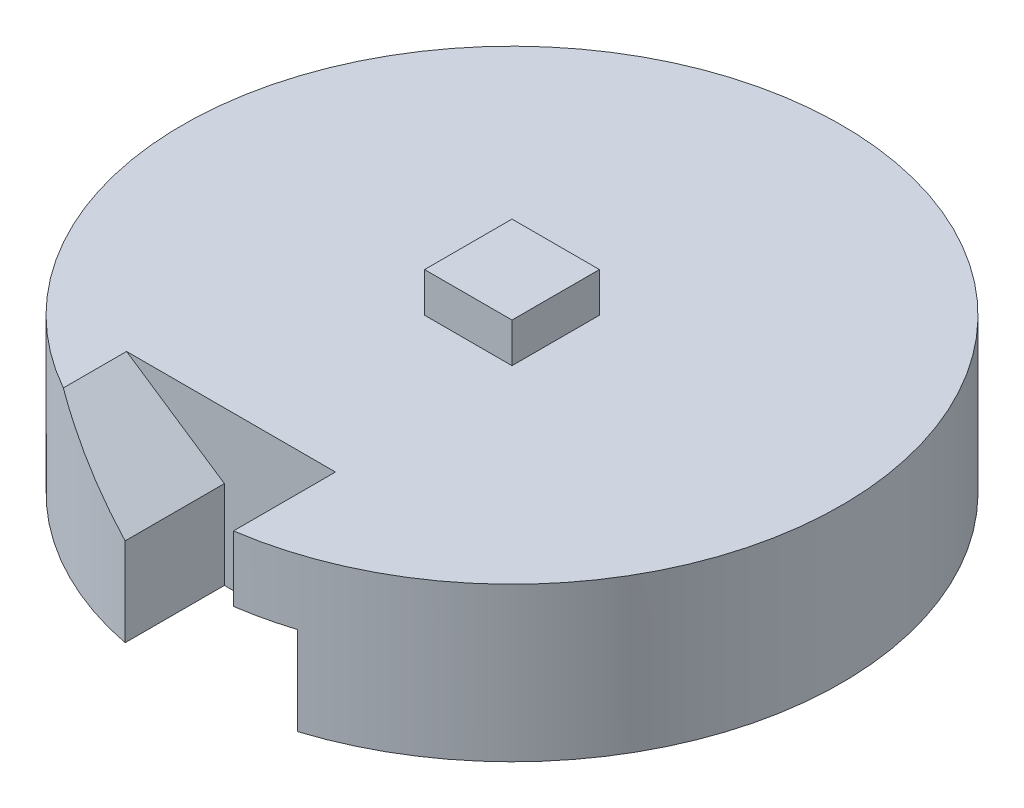
SolidWorks part; units mm, degrees
ref_plane "Front Plane" through (0, 0, 0) normal (0, 0, 1) x (1, 0, 0)
ref_plane "Top Plane" through (0, 0, 0) normal (0, 1, 0) x (1, 0, 0)
ref_plane "Right Plane" through (0, 0, 0) normal (1, 0, 0) x (0, 0, -1)
sketch "Sketch1" plane through (0, 0, 0) normal (0, 1, 0) x (1, 0, 0)
  circle A0 centre (0, 0) radius 37.5
extrude "Boss-Extrude1" add sketch "Sketch1" along normal blind 17.5 contours A0
sketch "Sketch2" plane through (0, 0, 0) normal (0, -1, 0) x (1, 0, 0)
  circle A0 centre (0, 0) radius 5
sketch "Sketch3" plane through (0, 17.5, 0) normal (0, 1, 0) x (1, 0, 0)
  line L0 (0, -75) -> (0, -65)
  line L1 (0, -65) -> (11.5, -65)
  line L2 (0, -65) -> (-11.5, -65)
  line L3 (-11.5, -65) -> (-11.5, -73.5674)
  line L4 (11.5, -65) -> (11.5, -73.5674)
  arc A0 (-37.5, 0) -> (37.5, 0) centre (0, -28.125) ccw
  circle A1 centre (0, 0) radius 37.5 construction
ref_plane "Plane1" through (0, 0, 37.5) normal (0, 0, 1) x (1, 0, 0)
sketch "Sketch7" plane through (0, 0, 37.5) normal (0, 0, 1) x (1, 0, 0)
  line L8 (5.4092, 17.6699) -> (-18.6153, 17.6699)
  line L18 (-18.6153, 17.6699) -> (-7.232, 10.0401)
  line L19 (5.4092, 17.6699) -> (5.4092, 10.0587)
  line L20 (5.4092, 10.0587) -> (11.3378, 10.0587)
  line L21 (11.3378, 10.0587) -> (11.3378, -0.1861)
  line L22 (-7.232, 10.0401) -> (-7.232, -0.1861)
  line L23 (-7.232, -0.1861) -> (11.3378, -0.1861)
extrude "Cut-Extrude3" cut sketch "Sketch7" against normal blind 12
sketch "Sketch9" plane through (0, 0, 0) normal (0, 1, 0) x (1, 0, 0)
  line L1 (-4.975, 4.975) -> (4.975, 4.975)
  line L2 (-4.975, 4.975) -> (-4.975, -4.975)
  line L3 (-4.975, -4.975) -> (4.975, -4.975)
  line L4 (4.975, 4.975) -> (4.975, -4.975)
  line L5 (-4.975, 4.975) -> (4.975, -4.975) construction
  line L6 (-4.975, -4.975) -> (4.975, 4.975) construction
  point P0 (0, 0)
  dimension "D1" = 9.95
  dimension "D2" = 9.95
extrude "Boss-Extrude2" add sketch "Sketch9" along normal blind 22
extrude "Boss-Extrude3" add sketch "Sketch2" along normal blind 10 contours A0
sketch "Sketch11" plane through (0, -10, 0) normal (0, -1, 0) x (1, 0, 0)
  line L0 (0.018, -1.4432) -> (0.5657, -1.4432)
  line L1 (0.018, -1.4432) -> (-0.5297, -1.4432)
  arc A0 (0.5657, -1.4432) -> (-0.5297, -1.4432) centre (0.018, 0.0068) ccw
extrude "Cut-Extrude5" cut sketch "Sketch11" against normal blind 10 contours L0 A0 L1
sketch "Sketch12" plane through (0, 0, 0) normal (0, -1, 0) x (-1, 0, 0)
  circle A3 centre (-30.018, -0.0068) radius 3.025
  circle A4 centre (29.982, -0.0068) radius 3.025
extrude "Cut-Extrude6" cut sketch "Sketch12" against normal blind 1.6 contours A3 | A4
